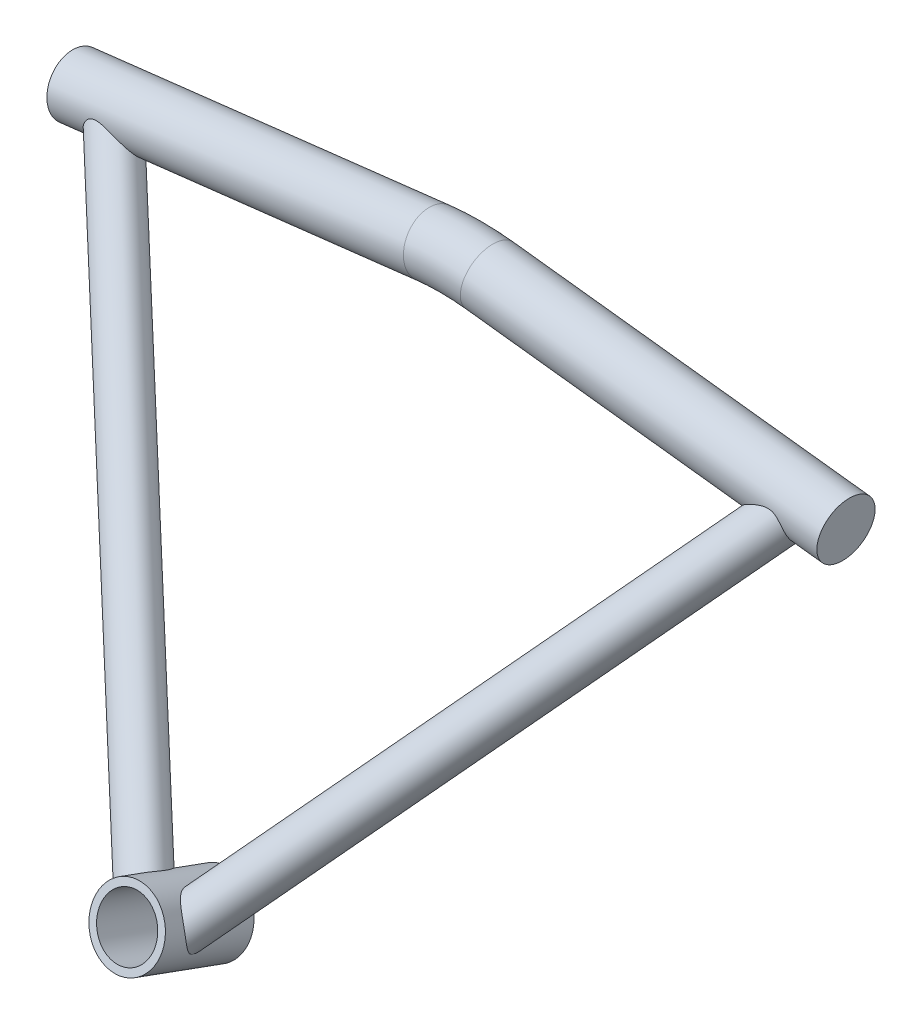
SolidWorks part; units mm, degrees
material "AISI 4130 Steel, normalized at 870C"
ref_plane "Front Plane" through (0, 0, 0) normal (0, 0, 1) x (1, 0, 0)
ref_plane "Top Plane" through (0, 0, 0) normal (0, 1, 0) x (1, 0, 0)
ref_plane "Right Plane" through (0, 0, 0) normal (1, 0, 0) x (0, 0, -1)
sketch "Sketch3" plane through (0, 0, 0) normal (0, 1, 0) x (1, 0, 0)
  line L0 (-5.08, -6.35) -> (5.08, -6.35) construction
  line L2 (0, -88.2205) -> (0, 88.2205) construction
  line L3 (5.08, 0) -> (-5.08, 0) construction
  dimension "D1" = 5.08
  dimension "D2" = 10.16
  dimension "D3" = 6.35
  dimension "D4" = 10.16
  dimension "D5" = 5.08
ref_plane "Plane1" through (0, 3.0668, 3.9968) normal (0, 0.6088, 0.7934) x (1, 0, 0)
ref_plane "Plane3" through (0, 0, 0) normal (0, 0.342, 0.9397) x (-1, 0, 0)
sketch "Sketch1" plane through (0, 0, 0) normal (0, 0.342, 0.9397) x (1, 0, 0)
  circle A0 centre (0, 0) radius 15.875
  dimension "D1" = 31.75
extrude "Boss-Extrude1" add sketch "Sketch1" along normal mid plane 41.402 contours A0
sketch "Sketch4" plane through (0, 3.0668, 3.9968) normal (0, 0.6088, 0.7934) x (1, 0, 0)
  line L0 (-5.08, -3.8656) -> (-154.2167, 217.2387)
  line L2 (0, -90.5202) -> (0, 90.5202) construction
  dimension "D2" = 34
  dimension "D3" = 266.7
sweep "Sweep1" add path "Sketch4" circular profile diameter 19.05 parameters "D3"=19.05
sketch "Sketch15" plane through (0, 3.0668, 3.9968) normal (0, 0.6088, 0.7934) x (1, 0, 0)
  line L0 (5.08, -3.8656) -> (154.2167, 217.2387)
  line L1 (0, -90.5202) -> (0, 90.5202) construction
  dimension "D1" = 266.7
  dimension "D2" = 34
sweep "Sweep2" add path "Sketch15" circular profile diameter 19.05 parameters "D3"=19.05
sketch "Sketch36" plane through (-148.9332, 175.1744, -134.416) normal (-0.5592, 0.6577, -0.5047) x (0.8288, 0.4283, -0.3601)
  circle A0 centre (-6.4966, -4.8776) radius 7.9375
  dimension "D1" = 15.875
extrude "Cut-Extrude2" cut sketch "Sketch36" against normal up to surface (276.6465 mm away) up to face at (15.3225, -2.4533, 5.398)
sketch "Sketch37" plane through (148.9332, 175.1744, -134.416) normal (0.5592, 0.6577, -0.5047) x (0.8288, -0.4283, 0.3601)
  circle A0 centre (6.4966, -4.8776) radius 7.9375
  dimension "D1" = 15.875
extrude "Cut-Extrude3" cut sketch "Sketch37" against normal up to surface (252.1497 mm away) up to face at (10.3244, -6.3916, 17.6978)
sketch "Sketch77" plane through (0, 7.0802, 19.4526) normal (0, 0.342, 0.9397) x (1, 0, 0)
  circle A1 centre (0, 0) radius 15.875
extrude "Boss-Extrude2" add sketch "Sketch77" against normal up to surface (41.402 mm away) up to face at (0, -21.9978, -14.023)
sketch "Sketch2" plane through (0, -7.0802, -19.4526) normal (0, -0.342, -0.9397) x (-1, 0, 0)
  circle A0 centre (0, 0) radius 12.7
  dimension "D1" = 25.4
extrude "Cut-Extrude1" cut sketch "Sketch2" against normal up to next
ref_plane "Plane2" through (0, 0, -127) normal (0, 0, 1) x (1, 0, 0)
sketch "Sketch40" plane through (-106.934, 0, -127) normal (0, 0, 1) x (1, 0, 0)
  line L2 (106.934, -90.5202) -> (106.934, 90.5202) construction
  line L3 (94.4643, 187.7402) -> (-61.9464, 169.4198)
  line L4 (119.4037, 187.7402) -> (275.8144, 169.4198)
  arc A0 (94.4643, 187.7402) -> (119.4037, 187.7402) centre (106.934, 81.28) cw
  point P0 (106.934, 188.468)
  point P7 (106.934, 188.468)
  dimension "D1" = 157.48
  dimension "D3" = 107.188
  dimension "D2" = 157.48
  dimension "D4" = 7.6
  dimension "D5" = 107.188
sweep "Sweep3" add path "Sketch40" circular profile diameter 25.4 parameters "D3"=25.4
